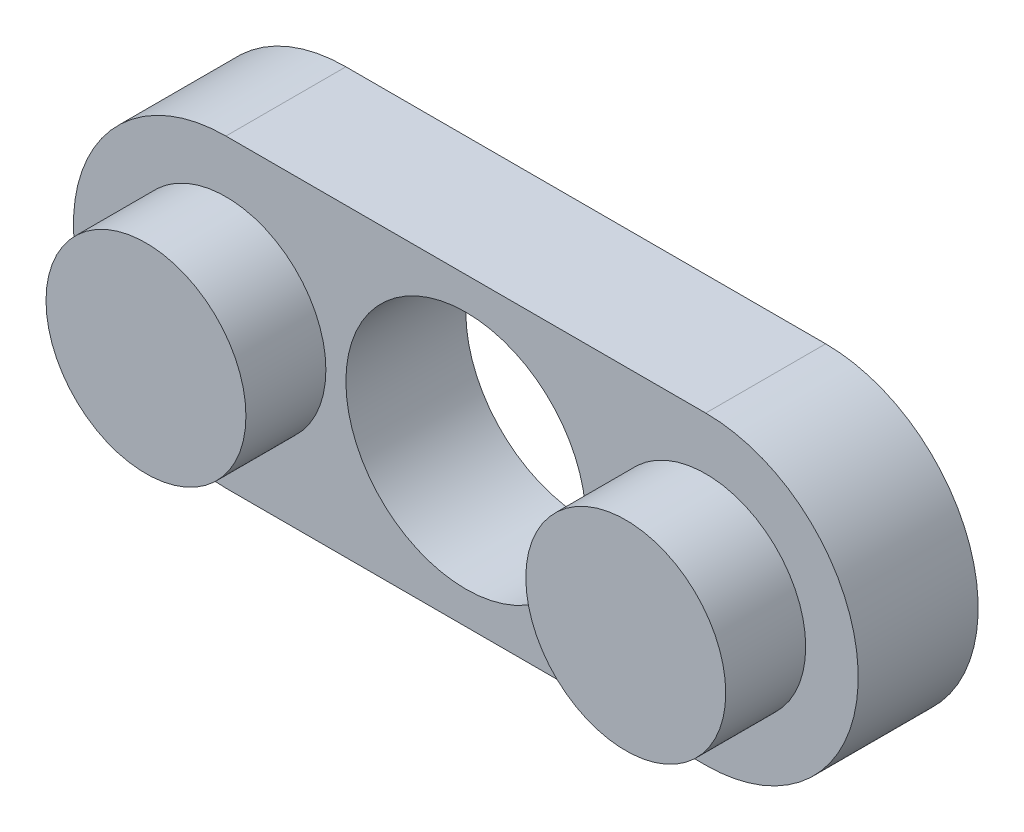
SolidWorks part; units mm, degrees
material "ASTM A36 Steel"
ref_plane "Front Plane" through (0, 0, 0) normal (0, 0, 1) x (1, 0, 0)
ref_plane "Top Plane" through (0, 0, 0) normal (0, 1, 0) x (1, 0, 0)
ref_plane "Right Plane" through (0, 0, 0) normal (1, 0, 0) x (0, 0, -1)
sketch "Sketch1" plane through (0, 0, 0) normal (0, 0, 1) x (1, 0, 0)
  line L0 (0, 0) -> (12, 0) construction
  line L1 (0, 3.8136) -> (12, 3.8136)
  line L2 (0, -3.8136) -> (12, -3.8136)
  arc A0 (0, 3.8136) -> (0, -3.8136) centre (0, 0) ccw
  arc A1 (12, -3.8136) -> (12, 3.8136) centre (12, 0) ccw
  circle A2 centre (0, 0) radius 2.5
  circle A3 centre (12, 0) radius 2.5
  point P3 (6, 0)
  dimension "D1" = 12
extrude "Boss-Extrude1" add sketch "Sketch1" against normal blind 3
extrude "Boss-Extrude2" add sketch "Sketch1<2>" along normal blind 2 and the other way up to surface (3 mm away) separate body contours A2 | A3 region at (0, 0, 0) region at (12, 0, 0) other way up to face at (14.5, 0, -3)
sketch "Sketch1<2>" plane through (0, 0, 0) normal (0, 0, 1) x (1, 0, 0) same geometry as "Sketch1"
sketch "Sketch2" plane through (0, 0, -3) normal (0, 0, -1) x (-1, 0, 0)
  circle A0 centre (-6, 0) radius 3
  point P2 (-4.6486, 0.5032)
extrude "Cut-Extrude1" cut sketch "Sketch2" against normal through all
